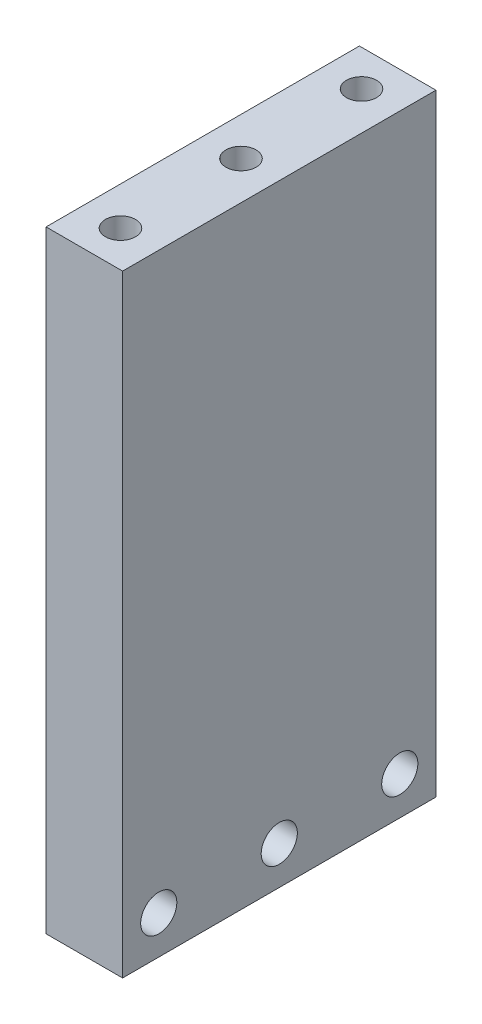
SolidWorks part; units mm, degrees
ref_plane "Front Plane" through (0, 0, 0) normal (0, 0, 1) x (1, 0, 0)
ref_plane "Top Plane" through (0, 0, 0) normal (0, 1, 0) x (1, 0, 0)
ref_plane "Right Plane" through (0, 0, 0) normal (1, 0, 0) x (0, 0, -1)
sketch "Sketch1" plane through (0, 0, 0) normal (0, 0, 1) x (1, 0, 0)
  line L1 (0, 0) -> (6.35, 0)
  line L2 (0, 0) -> (0, 50.8)
  line L3 (0, 50.8) -> (6.35, 50.8)
  line L4 (6.35, 0) -> (6.35, 50.8)
extrude "Boss-Extrude1" add sketch "Sketch1" along normal blind 26
sketch "Sketch4" plane through (6.35, 0, 0) normal (1, 0, 0) x (0, 0, -1)
  line L0 (0, 0) -> (0, 50.8) construction
  line L1 (-26, 0) -> (-26, 50.8) construction
  line L2 (-26, 0) -> (0, 0) construction
  circle A0 centre (-3, 3.175) radius 1.5
  circle A1 centre (-23, 3.175) radius 1.5
  dimension "D1" = 3
  dimension "D2" = 3
  dimension "D3" = 3
  dimension "D4" = 3
  dimension "D5" = 3.175
  dimension "D6" = 3.175
extrude "Cut-Extrude3" cut sketch "Sketch4" against normal blind 6.35
sketch "Sketch5" plane through (0, 50.8, 0) normal (0, 1, 0) x (1, 0, 0)
  line L0 (6.35, 0) -> (0, 0) construction
  line L1 (6.35, -26) -> (0, -26) construction
  line L2 (0, -26) -> (0, 0) construction
  circle A0 centre (3.175, -3) radius 1.25
  circle A1 centre (3.175, -23) radius 1.25
  dimension "D1" = 2.5
  dimension "D2" = 2.5
  dimension "D3" = 3
  dimension "D4" = 3
  dimension "D5" = 3.175
  dimension "D6" = 3.175
extrude "Cut-Extrude4" cut sketch "Sketch5" against normal blind 4
sketch "Sketch6" plane through (0, 0, 0) normal (-1, 0, 0) x (0, 0, 1)
  line L0 (26, 0) -> (0, 0) construction
  circle A0 centre (13, 3.175) radius 1.5
  circle A1 centre (3, 3.175) radius 1.5 construction
  dimension "D1" = 3
  dimension "D2" = 10
  dimension "D3" = 3.175
extrude "Cut-Extrude5" cut sketch "Sketch6" against normal blind 6.35
sketch "Sketch7" plane through (0, 50.8, 0) normal (0, 1, 0) x (1, 0, 0)
  line L0 (6.35, -26) -> (6.35, 0) construction
  circle A0 centre (3.175, -13) radius 1.25
  circle A1 centre (3.175, -3) radius 1.25 construction
  dimension "D1" = 2.5
  dimension "D2" = 10
  dimension "D3" = 3.175
extrude "Cut-Extrude6" cut sketch "Sketch7" against normal blind 4
